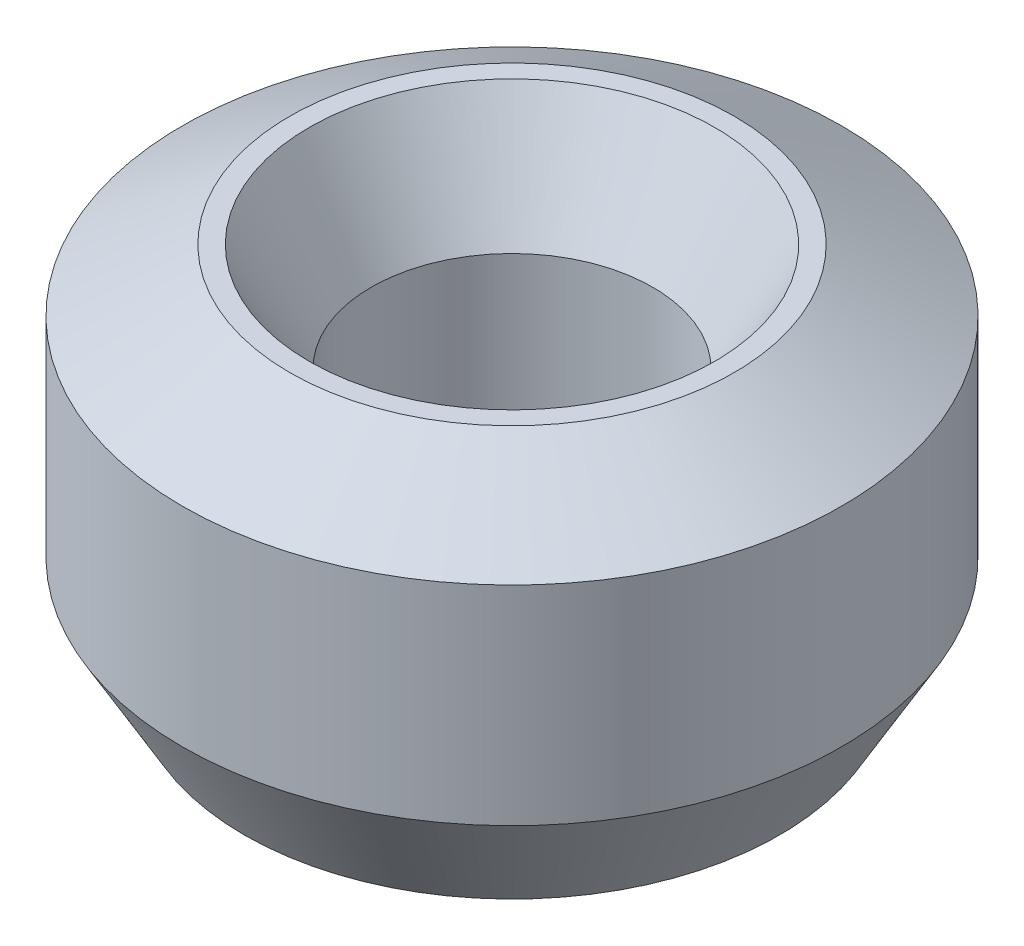
SolidWorks part; units mm, degrees
ref_plane "Front Plane" through (0, 0, 0) normal (0, 0, 1) x (1, 0, 0)
ref_plane "Top Plane" through (0, 0, 0) normal (0, 1, 0) x (1, 0, 0)
ref_plane "Right Plane" through (0, 0, 0) normal (1, 0, 0) x (0, 0, -1)
sketch "Sketch1" plane through (0, 0, 0) normal (0, 1, 0) x (1, 0, 0)
  circle A0 centre (0, 0) radius 7.5
  dimension "SLEEVE_OD" = 15
extrude "Boss-Extrude1" add sketch "Sketch1" along normal blind 8.5979
sketch "Sketch2" plane through (0, 0, 0) normal (0, 1, 0) x (1, 0, 0)
  circle A0 centre (0, 0) radius 3.2028
  dimension "BORE_D" = 6.4056
extrude "Cut-Extrude1" cut sketch "Sketch2" along normal through all
chamfer "Chamfer1" distance 1.411 angle 60 4 edges at (0, 8.5979, 3.2028) (0, 0, 3.2028) (0, 0, 7.5) (0, 8.5979, 7.5) first distance on face at (0, 8.5979, 3.2028) first distance on face at (0, 0, 3.2028) first distance on face at (0, 8.5979, 7.5)
